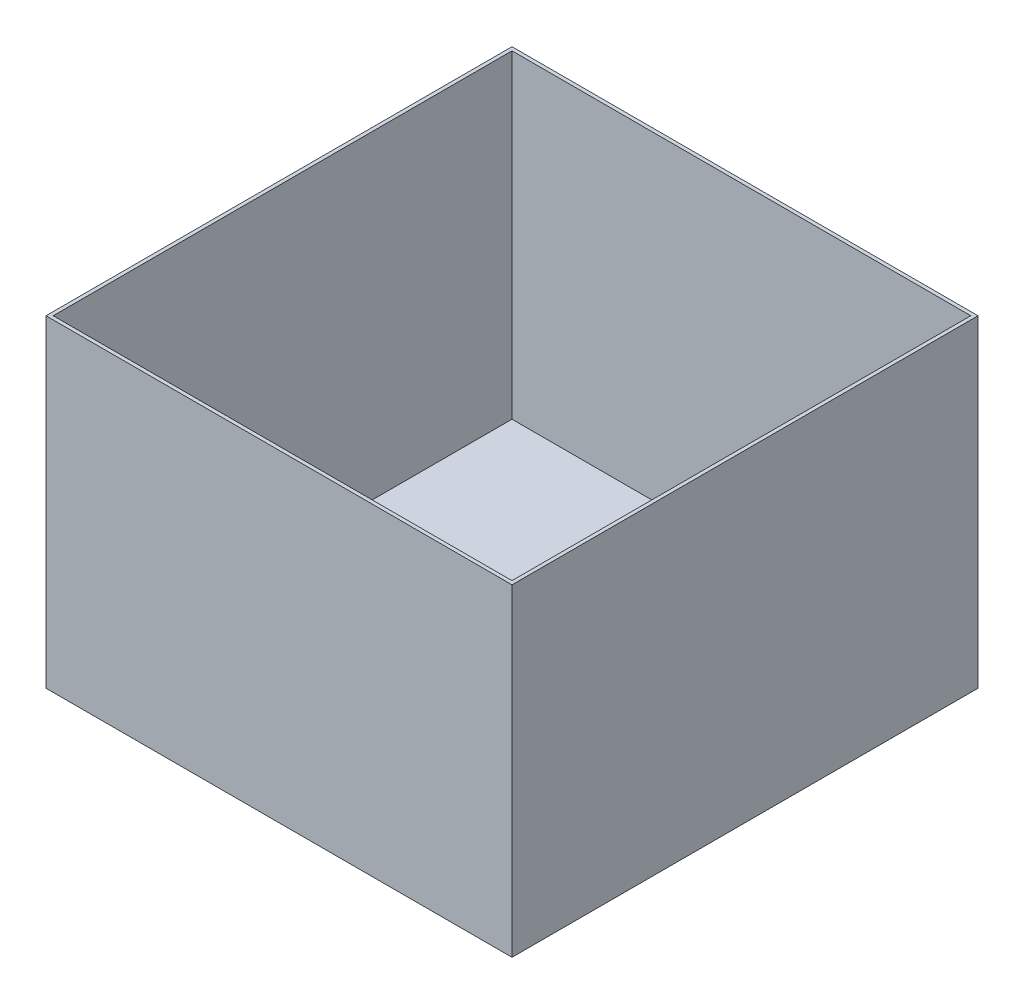
SolidWorks part; units mm, degrees
ref_plane "前视基准面" through (0, 0, 0) normal (0, 0, 1) x (1, 0, 0)
ref_plane "上视基准面" through (0, 0, 0) normal (0, 1, 0) x (1, 0, 0)
ref_plane "右视基准面" through (0, 0, 0) normal (1, 0, 0) x (0, 0, -1)
sketch "草图1" plane through (0, 0, 0) normal (0, 1, 0) x (1, 0, 0)
  line L0 (-130, 130) -> (130, -130) construction
  line L1 (-130, -130) -> (130, -130)
  line L2 (-130, -130) -> (-130, 130)
  line L3 (-130, 130) -> (130, 130)
  line L4 (130, -130) -> (130, 130)
  line L5 (130, 130) -> (-130, -130) construction
  point P5 (0, 0)
  dimension "D1" = 260
  dimension "D2" = 260
extrude "网" add sketch "草图1" along normal blind 2 contours L2 L3 L4 L1
extrude "网纵" add sketch "草图1<3>" along normal blind 180 thin thin type one direction reverse wall 2
sketch "草图1<3>" plane through (0, 0, 0) normal (0, 1, 0) x (1, 0, 0) same geometry as "草图1"
